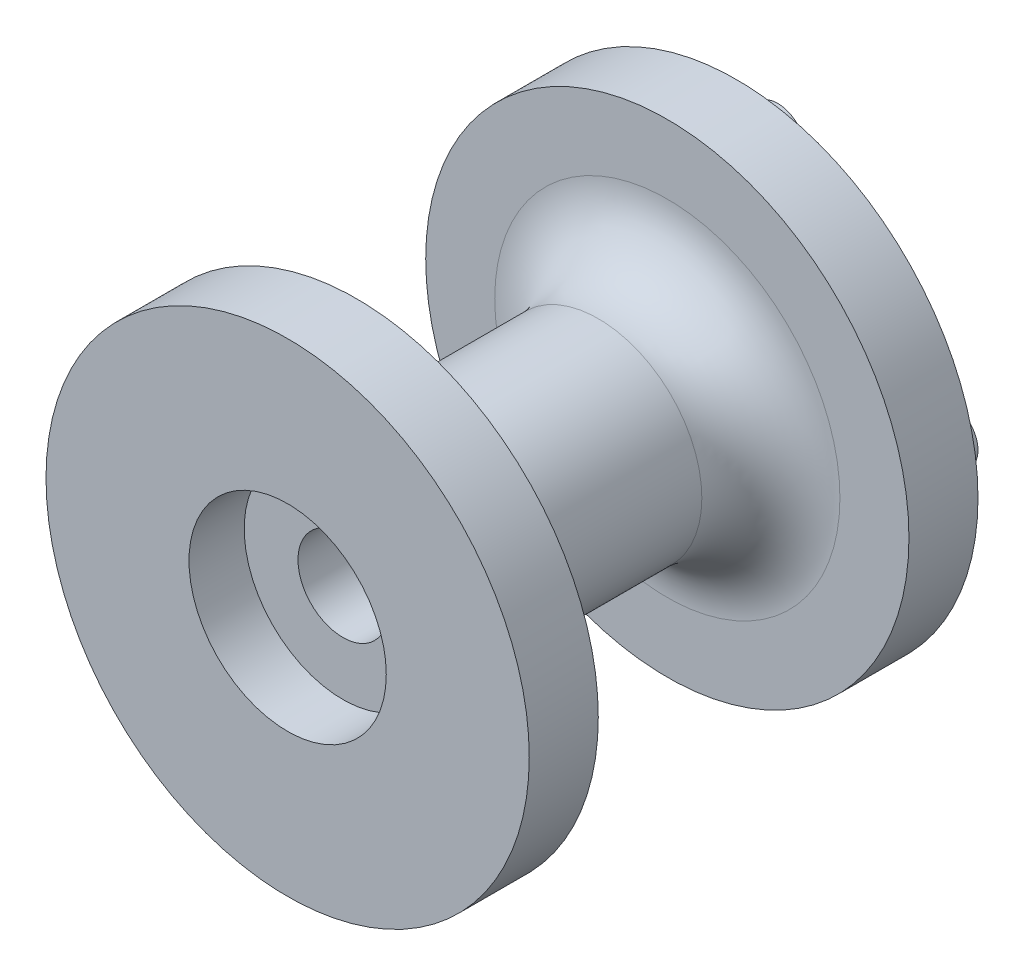
SolidWorks part; units mm, degrees
ref_plane "Plan de face" through (0, 0, 0) normal (0, 0, 1) x (1, 0, 0)
ref_plane "Plan de dessus" through (0, 0, 0) normal (0, 1, 0) x (1, 0, 0)
ref_plane "Plan de droite" through (0, 0, 0) normal (1, 0, 0) x (0, 0, -1)
sketch "Esquisse27" plane through (0, 0, 0) normal (1, 0, 0) x (0, 0, -1)
  line L1 (0, 0) -> (10, 0)
  line L2 (0, 0) -> (0, 35)
  line L3 (0, 35) -> (10, 35)
  line L4 (10, 0) -> (10, 35)
  line L5 (10, 0) -> (55, 0)
  line L6 (10, 0) -> (10, 15)
  line L7 (10, 15) -> (55, 15)
  line L8 (55, 0) -> (55, 15)
  line L9 (55, 0) -> (65, 0)
  line L10 (55, 0) -> (55, 35)
  line L11 (55, 35) -> (65, 35)
  line L12 (65, 0) -> (65, 35)
  line L13 (0, 0) -> (10, 0)
  line L14 (0, 0) -> (0, 14.29)
  line L15 (0, 14.29) -> (10, 14.29)
  line L16 (10, 0) -> (10, 14.29)
  line L17 (10, 0) -> (55, 0)
  line L18 (10, 0) -> (10, 6.5)
  line L19 (10, 6.5) -> (55, 6.5)
  line L20 (55, 0) -> (55, 6.5)
  line L21 (55, 0) -> (65, 0)
  line L22 (55, 0) -> (55, 14.29)
  line L23 (55, 14.29) -> (65, 14.29)
  line L24 (65, 0) -> (65, 14.29)
  line L25 (10, 15) -> (17, 15)
  line L26 (10, 15) -> (10, 22)
  line L27 (10, 22) -> (17, 22)
  line L28 (17, 15) -> (17, 22)
  line L29 (55, 15) -> (64.7359, 15)
  line L30 (55, 15) -> (55, 19.5012)
  line L31 (55, 19.5012) -> (64.7359, 19.5012)
  line L32 (64.7359, 15) -> (64.7359, 19.5012)
  line L33 (0, 14.29) -> (8, 14.29)
  line L34 (0, 14.29) -> (0, 0)
  line L35 (0, 0) -> (8, 0)
  line L36 (8, 14.29) -> (8, 0)
  line L37 (65, 14.29) -> (57, 14.29)
  line L38 (65, 14.29) -> (65, 0)
  line L39 (65, 0) -> (57, 0)
  line L40 (57, 14.29) -> (57, 0)
  dimension "D1" = 10
  dimension "D2" = 10
  dimension "D3" = 45
  dimension "D4" = 35
  dimension "D5" = 15
  dimension "D6" = 35
  dimension "D7" = 14.29
  dimension "D8" = 14.29
  dimension "D9" = 6.5
  dimension "D10" = 8
  dimension "D11" = 8
  dimension "D12" = 7
  dimension "D13" = 7
revolve "Révolution1" add sketch "Esquisse27" angle 360 about L5 region at (0, 7.145, -9) region at (0, 24.645, -5) region at (0, 10.75, -32.5) region at (0, 7.145, -56) region at (0, 26.6296, -60.0354)
sketch "Esquisse28" plane through (0, 0, -57) normal (0, 0, -1) x (-1, 0, 0)
  circle A0 centre (0, 0) radius 6.5
extrude "Enlèv. mat.-Extru.16" cut sketch "Esquisse28" against normal through all
fillet "Congé1" radius 10 1 edges at (15, 0, -10)
sketch "Esquisse29" plane through (0, 0, -65) normal (0, 0, -1) x (-1, 0, 0)
  circle A0 centre (0, 0) radius 25
  circle A1 centre (0, 25) radius 4
  circle A2 centre (25, 0) radius 4
  circle A3 centre (0, -25) radius 4
  circle A4 centre (-25, 0) radius 4
  dimension "D1" = 8
  dimension "D2" = 8
  dimension "D3" = 8
  dimension "D4" = 8
extrude "Boss.-Extru.1" add sketch "Esquisse29" along normal blind 6 contours A0 A4 | A0 A4 | A0 A1 | A0 A1 | A2 | A3 region at (0, 23.246, -65) region at (0, 26.6387, -65) region at (23.246, 0, -65) region at (26.6387, 0, -65)
sketch "Esquisse30" plane through (0, 0, -64.7359) normal (0, 0, 1) x (1, 0, 0)
  circle A0 centre (0, 0) radius 15
  circle A1 centre (0, 0) radius 19.5012
extrude "Boss.-Extru.2" add sketch "Esquisse30" along normal blind 9.7359
fillet "Congé2" radius 10 1 edges at (15, 0, -55)
